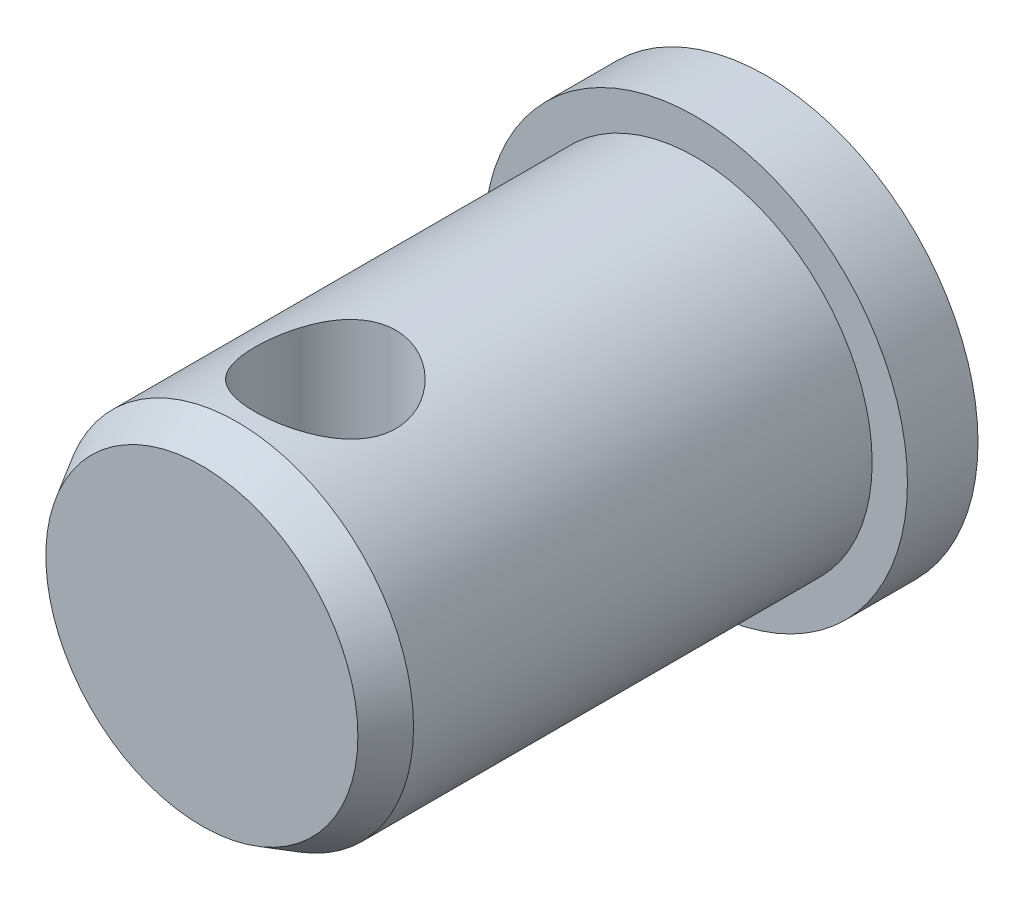
SolidWorks part; units mm, degrees
ref_plane "前基準面" through (0, 0, 0) normal (0, 0, 1) x (1, 0, 0)
ref_plane "上基準面" through (0, 0, 0) normal (0, 1, 0) x (1, 0, 0)
ref_plane "右基準面" through (0, 0, 0) normal (1, 0, 0) x (0, 0, -1)
sketch "草圖1" plane through (0, 0, 0) normal (0, 0, 1) x (1, 0, 0)
  circle A0 centre (0, 0) radius 3
  circle A1 centre (0, 0) radius 2.5
  dimension "D1" = 6
  dimension "D2" = 5
extrude "填料-伸長1" add sketch "草圖1" along normal blind 1 contours A0
extrude "填料-伸長2" add sketch "草圖1<3>" along normal blind 8 contours A1 region at (0, 0, 0)
sketch "草圖1<3>" plane through (0, 0, 0) normal (0, 0, 1) x (1, 0, 0) same geometry as "草圖1"
chamfer "導角1" distance 0.5 angle 30 1 edges at (2.5, 0, 8) first distance on face at (2.5, 0, 1)
sketch "草圖2" plane through (0, 0, 0) normal (0, 1, 0) x (1, 0, 0)
  line L2 (-2.2113, -8) -> (2.2113, -8) construction
  circle A0 centre (0, -6.25) radius 1
  point P4 (0, 0)
  dimension "D1" = 2
  dimension "D2" = 2.75
extrude "除料-伸長1" cut sketch "草圖2" against normal through all both and the other way through all
